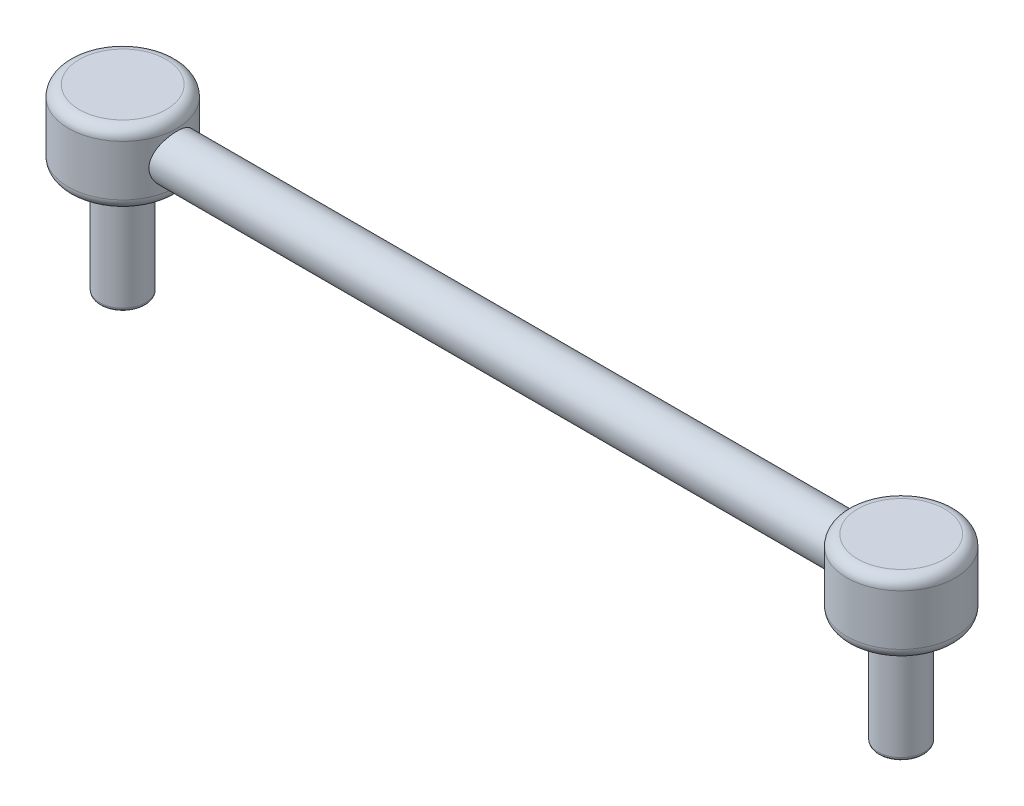
SolidWorks part; units mm, degrees
ref_plane "Front Plane" through (0, 0, 0) normal (0, 0, 1) x (1, 0, 0)
ref_plane "Top Plane" through (0, 0, 0) normal (0, 1, 0) x (1, 0, 0)
ref_plane "Right Plane" through (0, 0, 0) normal (1, 0, 0) x (0, 0, -1)
sketch "Sketch1" plane through (0, 0, 0) normal (0, 1, 0) x (1, 0, 0)
  circle A0 centre (0, 0) radius 6.35
  dimension "D1" = 12.7
extrude "Boss-Extrude1" add sketch "Sketch1" against normal blind 30
sketch "Sketch2" plane through (0, 0, 0) normal (0, 1, 0) x (1, 0, 0)
  circle A0 centre (0, 0) radius 15
  dimension "D1" = 30
extrude "Boss-Extrude2" add sketch "Sketch2" along normal blind 20
sketch "Sketch3" plane through (0, 0, 0) normal (0, 1, 0) x (1, 0, 0)
  point P0 (215, 0)
  dimension "D1" = 215
sketch "Sketch4" plane through (0, 0, 0) normal (0, 1, 0) x (1, 0, 0)
  circle A0 centre (215, 0) radius 6.35
  dimension "D1" = 12.7
extrude "Boss-Extrude3" add sketch "Sketch4" against normal blind 30 separate body
sketch "Sketch5" plane through (0, 0, 0) normal (0, 1, 0) x (1, 0, 0)
  circle A0 centre (215, 0) radius 15
  dimension "D1" = 30
extrude "Boss-Extrude4" add sketch "Sketch5" along normal blind 20
sketch "Sketch6" plane through (0, 0, 0) normal (1, 0, 0) x (0, 0, -1)
  circle A0 centre (0, 10) radius 6.35
  dimension "D1" = 12.7
  dimension "D2" = 10
extrude "Boss-Extrude5" add sketch "Sketch6" along normal blind 215
fillet "Fillet1" radius 3 4 edges at (215, 0, 15) (0, 0, 15) (0, 20, 15) (215, 20, 15)
fillet "Fillet2" radius 1 2 edges at (215, -30, 6.35) (0, -30, 6.35)
equation "\"pegDiameter\"= 1in / 2"
equation "\"rodDiameter\"= 1in / 2"
equation "\"rodLength\" = 215mm"
equation "\"D1@Sketch1\"=\"pegDiameter\""
equation "\"D1@Sketch3\"=\"rodLength\""
equation "\"D1@Sketch4\"=\"pegDiameter\""
equation "\"D1@Sketch6\"=\"rodDiameter\""
equation "\"D1@Boss-Extrude5\"=\"rodLength\""
